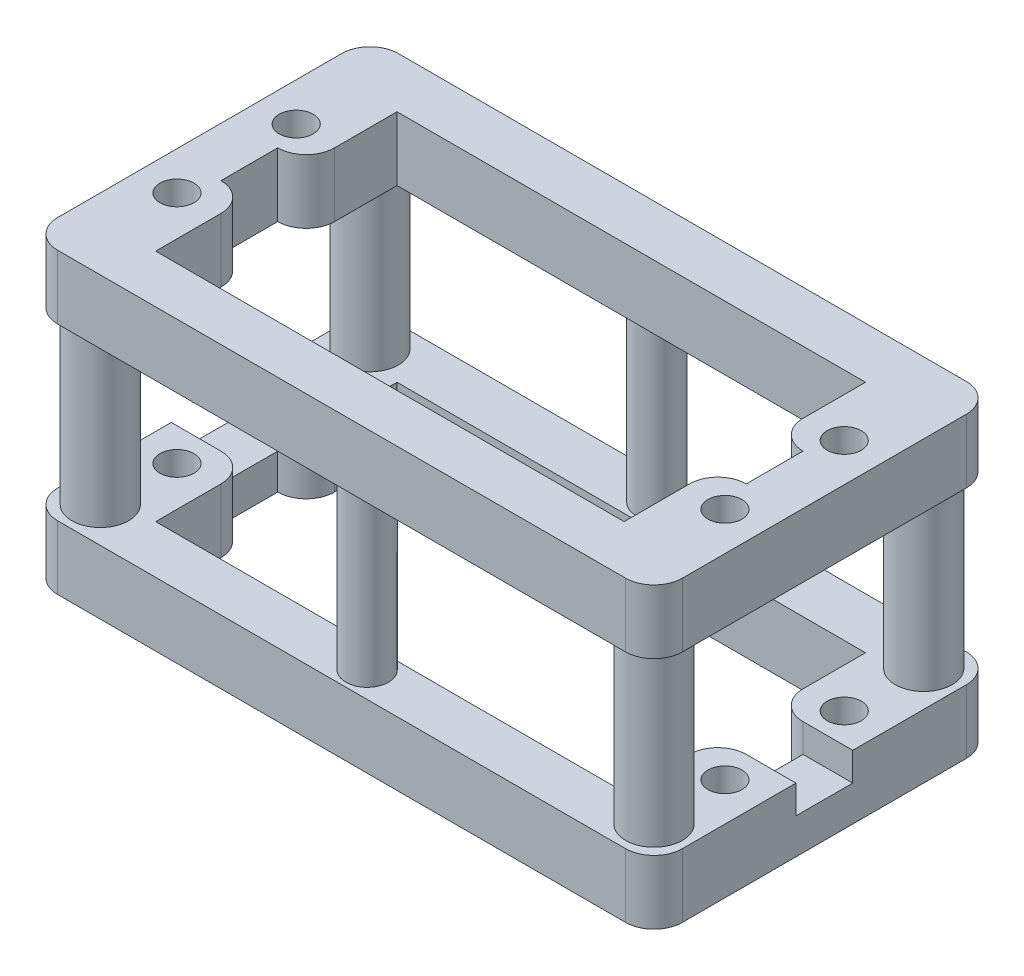
SolidWorks part; units mm, degrees
ref_plane "Front Plane" through (0, 0, 0) normal (0, 0, 1) x (1, 0, 0)
ref_plane "Top Plane" through (0, 0, 0) normal (0, 1, 0) x (1, 0, 0)
ref_plane "Right Plane" through (0, 0, 0) normal (1, 0, 0) x (0, 0, -1)
sketch "Sketch1" plane through (0, 0, 0) normal (0, 1, 0) x (1, 0, 0)
  line L1 (-27.94, -15.24) -> (27.94, -15.24)
  line L2 (-27.94, -15.24) -> (-27.94, 15.24)
  line L3 (-27.94, 15.24) -> (27.94, 15.24)
  line L4 (27.94, -15.24) -> (27.94, 15.24)
  line L5 (0, 15.24) -> (0, -15.24) construction
  line L6 (-27.94, 0) -> (27.94, 0) construction
  point P0 (0, 0)
  dimension "D1" = 55.88
  dimension "D2" = 30.48
extrude "Boss-Extrude1" add sketch "Sketch1" along normal mid plane 26.67 contours L1 L4 L3 L2
sketch "Sketch2" plane through (0, 13.335, 0) normal (0, 1, 0) x (1, 0, 0)
  line L0 (-20.955, 2.54) -> (-20.955, -2.54) construction
  line L1 (-20.955, -10.922) -> (20.955, -10.922)
  line L2 (-20.955, -10.922) -> (-20.955, -2.54)
  line L3 (-20.955, 10.668) -> (20.955, 10.668)
  line L4 (20.955, -10.922) -> (20.955, -2.54)
  line L5 (0, 10.668) -> (0, -10.922) construction
  line L6 (-20.955, 0) -> (20.955, 0) construction
  line L7 (-20.955, 2.54) -> (-23.495, 2.54)
  line L8 (-23.495, 2.54) -> (-23.495, -2.54)
  line L9 (-23.495, -2.54) -> (-20.955, -2.54)
  line L10 (-20.955, 2.54) -> (-20.955, 10.668)
  line L11 (23.495, -2.54) -> (20.955, -2.54)
  line L12 (23.495, 2.54) -> (23.495, -2.54)
  line L13 (20.955, 2.54) -> (23.495, 2.54)
  line L14 (20.955, 2.54) -> (20.955, 10.668)
  line L15 (-27.94, 15.24) -> (27.94, 15.24) construction
  point P0 (0, 0)
  point P6 (-20.955, 0)
  point P7 (-20.955, 0)
  point P8 (-20.955, 0)
  dimension "D1" = 21.59
  dimension "D2" = 41.91
  dimension "D3" = 5.08
  dimension "D4" = 2.54
  dimension "D5" = 5.08
  dimension "D6" = 4.572
extrude "Cut-Extrude1" cut sketch "Sketch2" against normal blind 26.67
sketch "Sketch3" plane through (0, 0, 15.24) normal (0, 0, 1) x (1, 0, 0)
  line L0 (27.94, 13.335) -> (27.94, -13.335) construction
  line L1 (-27.94, -7.62) -> (27.94, -7.62)
  line L2 (-27.94, -7.62) -> (-27.94, 7.62)
  line L3 (-27.94, 7.62) -> (27.94, 7.62)
  line L4 (27.94, -7.62) -> (27.94, 7.62)
  line L5 (0, 7.62) -> (0, -7.62) construction
  line L6 (-27.94, 0) -> (27.94, 0) construction
  point P0 (0, 0)
  dimension "D1" = 15.24
extrude "Cut-Extrude2" cut sketch "Sketch3" against normal up to surface (30.48 mm away) up to face at (0, 0, -15.24)
sketch "Sketch4" plane through (27.94, 0, 0) normal (1, 0, 0) x (0, 0, -1)
  line L0 (0, -7.62) -> (0, -13.335) construction
  line L1 (15.24, -7.62) -> (-15.24, -7.62) construction
  line L2 (-15.24, -13.335) -> (15.24, -13.335) construction
  line L4 (-12.7, -10.16) -> (12.7, -10.16)
  line L5 (-12.7, -10.16) -> (-12.7, -13.335)
  line L6 (-12.7, -13.335) -> (12.7, -13.335)
  line L7 (12.7, -10.16) -> (12.7, -13.335)
  line L8 (0, -13.335) -> (0, -10.16) construction
  line L9 (-12.7, -11.7475) -> (12.7, -11.7475) construction
  point P6 (0, -11.7475)
  dimension "D1" = 3.175
  dimension "D2" = 25.4
extrude "Boss-Extrude2" [suppressed] add sketch "Sketch4" along normal blind 7.62
sketch "Sketch5" plane through (-27.94, 0, 0) normal (-1, 0, 0) x (0, 0, 1)
  line L0 (0, -7.62) -> (0, -13.335) construction
  line L1 (-15.24, -7.62) -> (15.24, -7.62) construction
  line L2 (15.24, -13.335) -> (-15.24, -13.335) construction
  line L4 (-12.7, -13.335) -> (12.7, -13.335)
  line L5 (-12.7, -13.335) -> (-12.7, -10.16)
  line L6 (-12.7, -10.16) -> (12.7, -10.16)
  line L7 (12.7, -13.335) -> (12.7, -10.16)
  line L8 (0, -10.16) -> (0, -13.335) construction
  line L9 (-12.7, -11.7475) -> (12.7, -11.7475) construction
  point P6 (0, -11.7475)
  dimension "D1" = 3.175
  dimension "D2" = 25.4
extrude "Boss-Extrude3" [suppressed] add sketch "Sketch5" along normal blind 7.62
sketch "Sketch6" plane through (0, -7.62, 0) normal (0, 1, 0) x (1, 0, 0)
  line L0 (-27.94, 15.24) -> (-27.94, -15.24) construction
  line L1 (-27.94, -15.24) -> (27.94, -15.24) construction
  line L2 (27.94, 15.24) -> (27.94, -15.24) construction
  line L3 (-27.94, 15.24) -> (-27.94, -15.24) construction
  line L4 (-27.94, 15.24) -> (27.94, 15.24) construction
  line L5 (27.94, 15.24) -> (27.94, -15.24) construction
  circle A0 centre (-24.765, -12.065) radius 2.54
  circle A1 centre (24.765, -12.065) radius 2.54
  circle A2 centre (-24.765, 12.065) radius 2.54
  circle A3 centre (24.765, 12.065) radius 2.54
  circle A4 centre (0, -12.954) radius 1.905
  circle A5 centre (0, 12.954) radius 1.905
  point P22 (0, -15.24)
  dimension "D3" = 5.08
  dimension "D5" = 5.08
  dimension "D8" = 5.08
  dimension "D9" = 5.08
  dimension "D13" = 3.81
  dimension "D15" = 3.81
  dimension "D1" = 3.175
  dimension "D2" = 3.175
  dimension "D4" = 3.175
  dimension "D6" = 3.175
  dimension "D7" = 3.175
  dimension "D10" = 3.175
  dimension "D11" = 3.175
  dimension "D12" = 2.286
  dimension "D14" = 27.94
  dimension "D16" = 2.286
  dimension "D17" = 27.94
extrude "Boss-Extrude4" add sketch "Sketch6" along normal up to surface (15.24 mm away) up to face at (0, 7.62, 0)
sketch "Sketch7" [suppressed] plane through (0, -7.62, 0) normal (0, 1, 0) x (1, 0, 0)
  line L0 (35.56, 12.7) -> (35.56, -12.7) construction
  line L1 (35.56, -12.7) -> (27.94, -12.7) construction
  line L2 (-35.56, -12.7) -> (-35.56, 12.7) construction
  line L3 (-35.56, 12.7) -> (-27.94, 12.7) construction
  line L5 (35.56, 12.7) -> (27.94, 12.7) construction
  line L6 (-35.56, -12.7) -> (-27.94, -12.7) construction
  circle A0 centre (31.75, -5.08) radius 1.5875
  circle A1 centre (-31.75, 5.08) radius 1.5875
  circle A2 centre (31.75, 5.08) radius 1.5875
  circle A3 centre (-31.75, -5.08) radius 1.5875
  dimension "D1" = 3.175
  dimension "D4" = 3.175
  dimension "D7" = 3.175
  dimension "D12" = 3.175
  dimension "D2" = 3.81
  dimension "D3" = 7.62
  dimension "D5" = 3.81
  dimension "D6" = 7.62
  dimension "D8" = 3.81
  dimension "D9" = 7.62
  dimension "D10" = 7.62
  dimension "D11" = 3.81
  dimension "D13" = 10.16
extrude "Cut-Extrude3" [suppressed] cut sketch "Sketch7" against normal up to surface (5.08 mm away) up to face at (0, -13.335, 0.0423)
fillet "Fillet1" radius 2.54 8 edges at (-27.94, 10.4775, 15.24) (-27.94, 10.4775, -15.24) (27.94, 10.4775, -15.24) (27.94, 10.4775, 15.24) (-27.94, -10.4775, -15.24) (27.94, -10.4775, -15.24) (27.94, -10.4775, 15.24) (-27.94, -10.4775, 15.24)
fillet "Fillet2" radius 2.54 8 edges at (20.955, 10.4775, 2.54) (20.955, 10.4775, -2.54) (-20.955, 10.4775, 2.54) (-20.955, 10.4775, -2.54) (20.955, -10.4775, 2.54) (20.955, -10.4775, -2.54) (-20.955, -10.4775, 2.54) (-20.955, -10.4775, -2.54)
sketch "Sketch8" plane through (0, 13.335, 0) normal (0, 1, 0) x (1, 0, 0)
  line L0 (20.955, 5.08) -> (20.955, 10.668) construction
  line L1 (20.955, -10.922) -> (20.955, -5.08) construction
  line L2 (-20.955, 10.668) -> (-20.955, 5.08) construction
  line L3 (20.955, 10.668) -> (-20.955, 10.668) construction
  line L4 (-20.955, -10.922) -> (20.955, -10.922) construction
  circle A0 centre (-24.511, 5.207) radius 1.524
  circle A1 centre (-24.511, -5.461) radius 1.524
  circle A2 centre (24.511, 5.207) radius 1.524
  circle A3 centre (24.511, -5.461) radius 1.524
  dimension "D1" = 3.048
  dimension "D2" = 3.048
  dimension "D3" = 3.048
  dimension "D4" = 3.048
  dimension "D5" = 3.556
  dimension "D6" = 3.556
  dimension "D7" = 3.556
  dimension "D8" = 5.461
  dimension "D9" = 5.461
  dimension "D10" = 5.461
  dimension "D11" = 49.022
  dimension "D12" = 49.022
  dimension "D13" = 10.668
  dimension "D14" = 10.668
extrude "Cut-Extrude4" cut sketch "Sketch8" against normal up to surface (26.67 mm away) up to face at (0, -13.335, 0.0423)
fillet "Fillet3" [suppressed] radius 5.08
sketch "Sketch9" plane through (0, -7.62, 0) normal (0, 1, 0) x (1, 0, 0)
  line L0 (-27.94, 12.7) -> (-27.94, -12.7) construction
  line L1 (-23.495, -2.54) -> (-27.94, -2.54)
  line L2 (-23.495, -2.54) -> (-23.495, 2.54)
  line L3 (-23.495, 2.54) -> (-27.94, 2.54)
  line L4 (-27.94, -2.54) -> (-27.94, 2.54)
  line L5 (27.94, 12.7) -> (27.94, -12.7) construction
  line L6 (23.495, 2.54) -> (27.94, 2.54)
  line L7 (23.495, 2.54) -> (23.495, -2.54)
  line L8 (23.495, -2.54) -> (27.94, -2.54)
  line L9 (27.94, 2.54) -> (27.94, -2.54)
  dimension "D1" = 4.445
  dimension "D2" = 5.08
  dimension "D3" = 4.445
  dimension "D4" = 5.08
extrude "Cut-Extrude5" cut sketch "Sketch9" against normal blind 2.54
